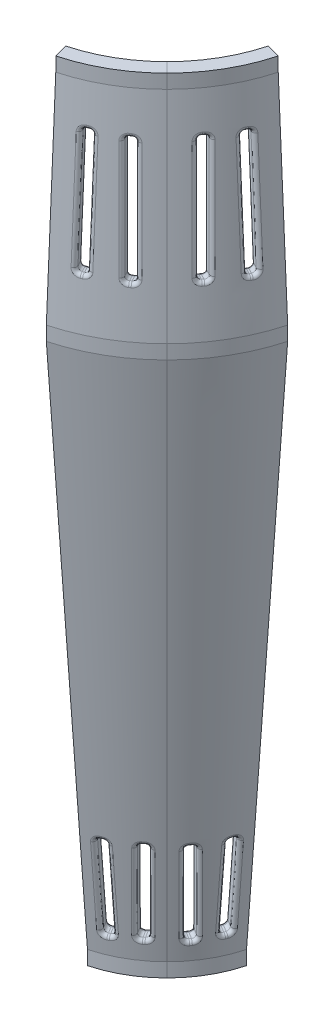
SolidWorks part; units mm, degrees
ref_plane "Front Plane" through (0, 0, 0) normal (0, 0, 1) x (1, 0, 0)
ref_plane "Top Plane" through (0, 0, 0) normal (0, 1, 0) x (1, 0, 0)
ref_plane "Right Plane" through (0, 0, 0) normal (1, 0, 0) x (0, 0, -1)
sketch "Sketch1" plane through (0, 0, 0) normal (0, 1, 0) x (1, 0, 0)
  line L0 (-28.2843, 28.2843) -> (-24.7487, 24.7487) construction
  line L1 (28.2843, 28.2843) -> (24.7487, 24.7487) construction
  line L2 (-24.7487, 24.7487) -> (0, 0) construction
  line L3 (24.7487, 24.7487) -> (0, 0) construction
  line L4 (0, 0) -> (0, 40) construction
  line L5 (-9.0587, -33.8074) -> (-10.3528, -38.637) construction
  line L6 (9.0587, -33.8074) -> (10.3528, -38.637)
  line L7 (0, 0) -> (9.0587, -33.8074) construction
  line L8 (0, 0) -> (-9.0587, -33.8074) construction
  line L9 (0, 0) -> (0, -40) construction
  line L10 (-24.7487, -24.7487) -> (-28.2843, -28.2843) construction
  line L11 (24.7487, -24.7487) -> (28.2843, -28.2843)
  line L12 (-24.7487, -24.7487) -> (0, 0) construction
  line L13 (0, 0) -> (24.7487, -24.7487) construction
  arc A0 (9.0587, -33.8074) -> (24.7487, -24.7487) centre (0, 0) ccw
  arc A1 (10.3528, -38.637) -> (28.2843, -28.2843) centre (0, 0) ccw
  arc A2 (-24.7487, -24.7487) -> (-9.0587, -33.8074) centre (0, 0) ccw construction
  arc A3 (-28.2843, -28.2843) -> (-10.3528, -38.637) centre (0, 0) ccw construction
  arc A4 (24.7487, 24.7487) -> (-24.7487, 24.7487) centre (0, 0) ccw construction
  arc A5 (28.2843, 28.2843) -> (-28.2843, 28.2843) centre (0, 0) ccw construction
  dimension "D1" = 70
  dimension "D2" = 5
  dimension "D3" = 45
  dimension "D4" = 45
  dimension "D5" = 15
  dimension "D6" = 15
  dimension "D7" = 30
  dimension "D8" = 30
ref_plane "Plane1" through (0, 210, 0) normal (0, 1, 0) x (1, 0, 0)
sketch "Sketch2" plane through (0, 210, 0) normal (0, 1, 0) x (1, 0, 0)
  line L0 (0, 0) -> (24.7487, -24.7487) construction
  line L1 (0, 0) -> (9.0587, -33.8074) construction
  line L2 (0, 0) -> (-9.0587, -33.8074) construction
  line L3 (-24.7487, -24.7487) -> (0, 0) construction
  line L4 (24.7487, 24.7487) -> (0, 0) construction
  line L5 (0, 0) -> (0, 40) construction
  line L6 (-24.7487, 24.7487) -> (0, 0) construction
  line L7 (0, 0) -> (24.7487, -24.7487) construction
  line L8 (0, 0) -> (9.0587, -33.8074) construction
  line L9 (0, 0) -> (-9.0587, -33.8074) construction
  line L10 (-24.7487, -24.7487) -> (0, 0) construction
  line L11 (24.7487, 24.7487) -> (0, 0) construction
  line L12 (0, 0) -> (0, 40) construction
  line L13 (-24.7487, 24.7487) -> (0, 0) construction
  line L14 (-42.9214, 42.9214) -> (-39.3858, 39.3858) construction
  line L15 (42.9214, 42.9214) -> (39.3858, 39.3858) construction
  line L16 (-39.3858, -39.3858) -> (-42.9214, -42.9214) construction
  line L17 (-14.4162, -53.8021) -> (-15.7103, -58.6317) construction
  line L18 (14.4162, -53.8021) -> (15.7103, -58.6317)
  line L19 (39.3858, -39.3858) -> (42.9214, -42.9214)
  arc A0 (-39.3858, -39.3858) -> (-14.4162, -53.8021) centre (0, 0) ccw construction
  arc A1 (-42.9214, -42.9214) -> (-15.7103, -58.6317) centre (0, 0) ccw construction
  arc A2 (39.3858, 39.3858) -> (-39.3858, 39.3858) centre (0, 0) ccw construction
  arc A3 (42.9214, 42.9214) -> (-42.9214, 42.9214) centre (0, 0) ccw construction
  arc A4 (14.4162, -53.8021) -> (39.3858, -39.3858) centre (0, 0) ccw
  arc A5 (15.7103, -58.6317) -> (42.9214, -42.9214) centre (0, 0) ccw
  dimension "D1" = 111.4
  dimension "D2" = 5
ref_plane "Plane2" through (0, 290, 0) normal (0, 1, 0) x (1, 0, 0)
sketch "Sketch3" plane through (0, 290, 0) normal (0, 1, 0) x (1, 0, 0)
  line L0 (-24.7487, -24.7487) -> (0, 0) construction
  line L1 (0, 0) -> (-9.0587, -33.8074) construction
  line L2 (0, 0) -> (9.0587, -33.8074) construction
  line L3 (0, 0) -> (24.7487, -24.7487) construction
  line L4 (24.7487, 24.7487) -> (0, 0) construction
  line L5 (0, 0) -> (0, 40) construction
  line L6 (-24.7487, 24.7487) -> (0, 0) construction
  line L7 (-24.7487, -24.7487) -> (0, 0) construction
  line L8 (0, 0) -> (-9.0587, -33.8074) construction
  line L9 (0, 0) -> (9.0587, -33.8074) construction
  line L10 (0, 0) -> (24.7487, -24.7487) construction
  line L11 (24.7487, 24.7487) -> (0, 0) construction
  line L12 (0, 0) -> (0, 40) construction
  line L13 (-24.7487, 24.7487) -> (0, 0) construction
  line L14 (-36.0271, 36.0271) -> (-39.5626, 39.5626) construction
  line L15 (39.5626, 39.5626) -> (36.0271, 36.0271) construction
  line L16 (-36.0271, -36.0271) -> (-39.5626, -39.5626) construction
  line L17 (-13.1868, -49.2139) -> (-14.4809, -54.0435) construction
  line L18 (13.1868, -49.2139) -> (14.4809, -54.0435)
  line L19 (36.0271, -36.0271) -> (39.5626, -39.5626)
  arc A0 (-36.0271, -36.0271) -> (-13.1868, -49.2139) centre (0, 0) ccw construction
  arc A1 (-39.5626, -39.5626) -> (-14.4809, -54.0435) centre (0, 0) ccw construction
  arc A2 (39.5626, 39.5626) -> (-39.5626, 39.5626) centre (0, 0) ccw construction
  arc A3 (36.0271, 36.0271) -> (-36.0271, 36.0271) centre (0, 0) ccw construction
  arc A4 (13.1868, -49.2139) -> (36.0271, -36.0271) centre (0, 0) ccw
  arc A5 (14.4809, -54.0435) -> (39.5626, -39.5626) centre (0, 0) ccw
  dimension "D1" = 101.9
  dimension "D2" = 5
extrude "Boss-Extrude1" add sketch "Sketch2" against normal blind 5
extrude "Boss-Extrude2" add sketch "Sketch1" along normal blind 5 separate body
loft "Loft4" add section face at (18.4306, 5, 31.9227) section face at (28.6042, 205, 49.544) connector at (10.3528, 5, 38.637) connector at (15.7103, 205, 58.6317)
extrude "Boss-Extrude3" add sketch "Sketch3" against normal blind 5 separate body
loft "Loft6" add section face at (28.6042, 210, 49.544) section face at (26.2697, 285, 45.5004) connector at (14.4162, 210, 53.8021) connector at (13.1868, 285, 49.2139)
ref_plane "Plane3" through (17.354, -3.1833, 30.058) normal (-0.4979, 0.0913, -0.8624) x (-0.8672, -0.0478, 0.4956)
sketch "Sketch9" plane through (17.354, -3.1833, 30.058) normal (-0.4979, 0.0913, -0.8624) x (-0.8672, -0.0478, 0.4956)
  line L0 (-24.4392, 208.1236) -> (-8.8517, 184.1082) construction
  line L1 (-8.8517, 184.1082) -> (4.36, 209.5082) construction
  line L2 (-24.4392, 208.1236) -> (4.36, 209.5082) construction
  line L7 (-3.6383, 185.8606) -> (9.0617, 186.4712)
  line L8 (-3.4942, 182.8641) -> (9.2058, 183.4747)
  line L29 (9.2058, 183.4747) -> (9.0617, 186.4712)
  line L31 (-14.065, 182.3558) -> (-26.765, 181.7453)
  line L32 (-26.765, 181.7453) -> (-26.9091, 184.7418)
  line L33 (-26.9091, 184.7418) -> (-14.2091, 185.3524)
  line L35 (-26.8371, 183.2435) -> (9.1337, 184.9729) construction
  line L36 (-9.4356, 7.6225) -> (8.6608, 8.4926) construction
  line L38 (-10.0396, 208.8159) -> (-0.3874, 8.0576) construction
  line L40 (-12.1441, 142.402) -> (-24.8441, 141.7914)
  line L41 (-24.8441, 141.7914) -> (-24.9882, 144.7879)
  line L42 (-24.9882, 144.7879) -> (-12.2882, 145.3985)
  line L43 (-1.7174, 145.9068) -> (10.9826, 146.5174)
  line L44 (11.1267, 143.5208) -> (10.9826, 146.5174)
  line L45 (-1.5733, 142.9102) -> (11.1267, 143.5208)
  line L46 (-10.2232, 102.4482) -> (-22.9232, 101.8376)
  line L47 (-22.9232, 101.8376) -> (-23.0672, 104.8341)
  line L48 (-23.0672, 104.8341) -> (-10.3672, 105.4447)
  line L49 (0.2036, 105.9529) -> (12.9036, 106.5635)
  line L50 (13.0476, 103.567) -> (12.9036, 106.5635)
  line L51 (0.3476, 102.9564) -> (13.0476, 103.567)
  line L52 (-8.3023, 62.4943) -> (-21.0023, 61.8837)
  line L53 (-21.0023, 61.8837) -> (-21.1463, 64.8803)
  line L54 (-21.1463, 64.8803) -> (-8.4463, 65.4909)
  line L55 (2.1245, 65.9991) -> (14.8245, 66.6097)
  line L56 (14.9685, 63.6131) -> (14.8245, 66.6097)
  line L57 (2.2685, 63.0025) -> (14.9685, 63.6131)
  arc A10 (-14.065, 182.3558) -> (-3.4942, 182.8641) centre (-8.8517, 184.1082) ccw
  arc A11 (-3.6383, 185.8606) -> (-14.2091, 185.3524) centre (-8.8517, 184.1082) ccw
  arc A12 (-1.7174, 145.9068) -> (-12.2882, 145.3985) centre (-6.9307, 144.1544) ccw
  arc A13 (-12.1441, 142.402) -> (-1.5733, 142.9102) centre (-6.9307, 144.1544) ccw
  arc A14 (0.2036, 105.9529) -> (-10.3672, 105.4447) centre (-5.0098, 104.2005) ccw
  arc A15 (-10.2232, 102.4482) -> (0.3476, 102.9564) centre (-5.0098, 104.2005) ccw
  arc A16 (2.1245, 65.9991) -> (-8.4463, 65.4909) centre (-3.0889, 64.2467) ccw
  arc A17 (-8.3023, 62.4943) -> (2.2685, 63.0025) centre (-3.0889, 64.2467) ccw
  dimension "D1" = 11
  dimension "D2" = 25.4
  dimension "D3" = 3
  dimension "D4" = 12.7
  dimension "D5" = 4
extrude "Cut-Extrude3" cut sketch "Sketch9" against normal blind 3 and the other way blind 3
ref_plane "Plane4" through (36.1255, 5.8578, 62.5712) normal (0.4984, 0.0808, 0.8632) x (0.8669, -0.0372, -0.497)
sketch "Sketch10" plane through (36.1255, 5.8578, 62.5712) normal (0.4984, 0.0808, 0.8632) x (0.8669, -0.0372, -0.497)
  line L0 (-2.8039, 264.8198) -> (-0.4945, 221.8672)
  line L9 (-0.4945, 221.8672) -> (-3.6695, 221.8672)
  line L10 (-3.6695, 221.8672) -> (-5.9789, 264.8198)
  line L11 (-5.9789, 264.8198) -> (-2.8039, 264.8198)
  line L16 (6.7522, 205.3608) -> (2.7183, 280.388) construction
  line L17 (-13.8045, 264.8198) -> (-16.9795, 264.8198)
  line L18 (-16.9795, 264.8198) -> (-16.0778, 221.8672)
  line L19 (-16.0778, 221.8672) -> (-12.9028, 221.8672)
  line L20 (-12.9028, 221.8672) -> (-13.8045, 264.8198)
  line L21 (-22.0601, 204.2841) -> (-23.637, 279.4031) construction
  ellipse E0 centre (-10.6079, 283.8698) end of major axis (-61.5224, 281.9671) minor radius 4.1173 (-23.637, 279.4031) -> (2.7183, 280.388) ccw construction
  ellipse E1 centre (-7.8163, 209.1672) end of major axis (-63.4775, 207.0872) minor radius 4.5012 (-22.0601, 204.2841) -> (6.7522, 205.3608) ccw construction
  dimension "D1" = 19.05
  dimension "D2" = 12.7
  dimension "D3" = 3.175
  dimension "D4" = 6.35
  dimension "D5" = 6.35
  dimension "D6" = 6.35
  dimension "D7" = 6.35
  dimension "D8" = 19.05
  dimension "D9" = 12.7
  dimension "D10" = 3.175
extrude "Cut-Extrude4" cut sketch "Sketch10" against normal through all both and the other way through all
sketch "Sketch11" plane through (17.354, -3.1833, 30.058) normal (-0.4979, 0.0913, -0.8624) x (-0.8672, -0.0478, 0.4956)
  line L0 (-9.1835, 46.8021) -> (-6.8138, 15.1334)
  line L1 (-6.8138, 15.1334) -> (-3.6388, 15.1334)
  line L2 (-3.6388, 15.1334) -> (-6.0085, 46.8021)
  line L3 (-6.0085, 46.8021) -> (-9.1835, 46.8021)
  line L4 (1.4887, 46.8834) -> (2.168, 15.1334)
  line L5 (2.168, 15.1334) -> (5.343, 15.1334)
  line L6 (5.343, 15.1334) -> (4.6637, 46.8834)
  line L7 (4.6637, 46.8834) -> (1.4887, 46.8834)
  line L8 (-9.4356, 7.6225) -> (-13.5229, 62.2433) construction
  line L9 (8.6608, 8.4926) -> (7.4892, 63.2535) construction
  ellipse E0 centre (-0.2391, 4.9734) end of major axis (-35.1987, 3.2925) minor radius 3.1967 (8.6608, 8.4926) -> (-9.4356, 7.6225) ccw construction
  dimension "D1" = 3.175
  dimension "D2" = 3.175
  dimension "D3" = 3.175
  dimension "D4" = 3.175
  dimension "D5" = 3.175
  dimension "D6" = 31.75
  dimension "D7" = 10.16
  dimension "D8" = 10.16
extrude "Cut-Extrude5" cut sketch "Sketch11" along normal through all and the other way through all
fillet "Fillet1" radius 1.27 48 edges at (21.7557, 227.381, 50.0776) (21.0372, 270.263, 47.427) (23.5376, 270.6684, 51.7569) (24.2581, 227.7867, 54.4109) (32.5129, 226.9182, 43.8997) (35.0146, 227.3239, 48.2335) (32.4614, 227.1926, 46.9883) (21.5359, 227.6271, 52.8642) (20.8218, 270.5099, 50.2215) (23.7339, 270.4176, 48.9199) (24.4601, 227.5368, 51.5835) (30.5744, 269.8527, 41.9498) (30.5153, 270.1258, 45.0253) (33.0741, 270.2581, 46.2802) (33.106, 269.9814, 43.1668) (35.04, 227.0462, 45.109) (13.8261, 11.7497, 32.9125) (16.3207, 11.2924, 37.2312) (17.1841, 42.8788, 40.4192) (14.6861, 43.3368, 36.0945) (23.9503, 43.7664, 30.7952) (26.4467, 43.3083, 35.121) (24.1175, 11.7219, 32.7793) (21.6246, 12.1794, 28.4595) (17.4028, 43.1679, 37.6195) (16.5308, 11.583, 34.4167) (13.5899, 11.4655, 35.6657) (14.444, 43.0537, 38.8374) (21.5676, 11.8605, 31.5406) (23.9052, 43.4454, 33.897) (26.4548, 43.6346, 31.9704) (24.1351, 12.0464, 29.6449)
pattern_circular "CirPattern8" count 2 over 330 about axis through (0, 290, 0) along (0, -1, 0) of bodies 124 120
